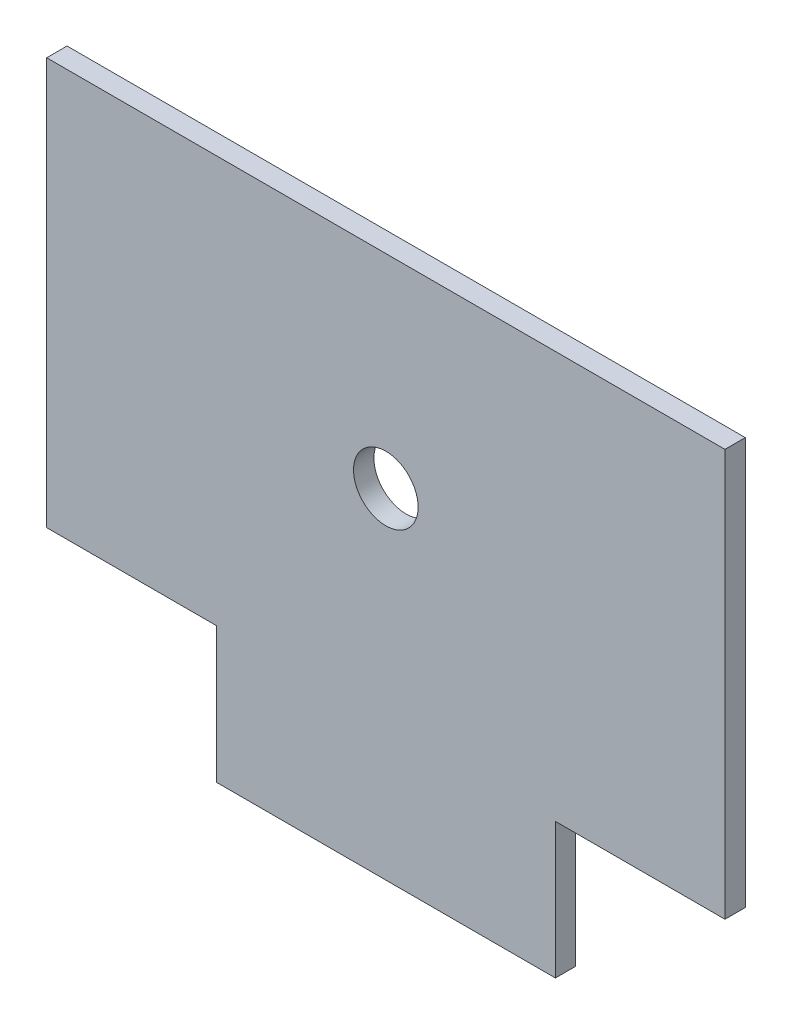
SolidWorks part; units mm, degrees
ref_plane "Front Plane" through (0, 0, 0) normal (0, 0, 1) x (1, 0, 0)
ref_plane "Top Plane" through (0, 0, 0) normal (0, 1, 0) x (1, 0, 0)
ref_plane "Right Plane" through (0, 0, 0) normal (1, 0, 0) x (0, 0, -1)
sketch "Sketch1" plane through (0, 0, 0) normal (0, 0, 1) x (1, 0, 0)
  line L0 (-50, 0) -> (-50, -60)
  line L1 (-50, -60) -> (-25, -60)
  line L2 (-25, -60) -> (-25, -80)
  line L3 (-25, -80) -> (25, -80)
  line L4 (25, -80) -> (25, -60)
  line L5 (25, -60) -> (50, -60)
  line L6 (50, -60) -> (50, 0)
  line L7 (50, 0) -> (-50, 0)
  line L8 (0, 24.4437) -> (0, -96.3194) construction
  line L9 (-50, -30) -> (50, -30) construction
  point P2 (0, 0)
  point P9 (0, -30)
  point P11 (0, -30)
  point P16 (0, 0)
  point P17 (0, -96.3194)
  point P18 (0, 0)
  dimension "D1" = 60
  dimension "D2" = 50
  dimension "D3" = 20
  dimension "D4" = 25
extrude "Boss-Extrude1" add sketch "Sketch1" along normal blind 3
hole_wizard "3/8 (0.3750) Dowel Hole1" positions "Sketch2" profile "Sketch3" hole size "3/8" standard "ANSI Inch" end condition through all
sketch "Sketch2" plane through (0, 0, 3) normal (0, 0, 1) x (1, 0, 0)
  point P0 (0, -30)
sketch "Sketch3" plane through (0, -30, 3) normal (1, 0, 0) x (0, -1, 0)
  line L0 (0, 0) -> (0, 3)
  line L1 (0, 3) -> (4.7625, 3)
  line L2 (4.7625, 3) -> (4.7625, 0)
  line L5 (4.7625, 0) -> (0, 0)
  line L11 (0, -6.35) -> (0, 107.95) construction
  dimension "Thru Hole Dia." = 9.525
  dimension "Thru Hole Depth" = 3
